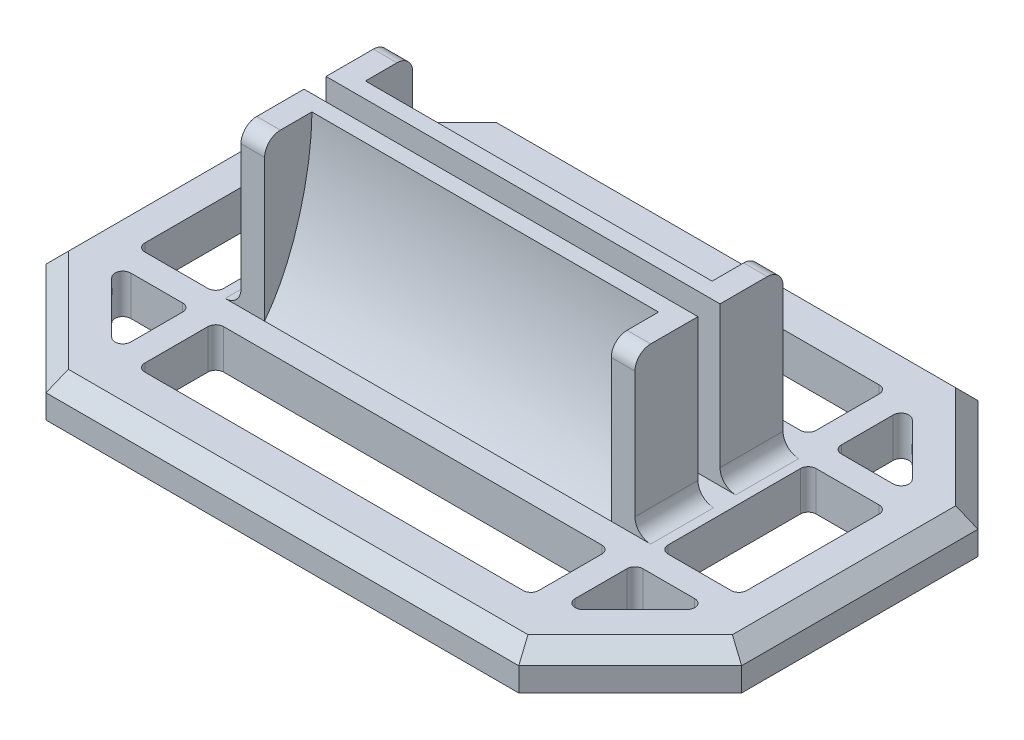
SolidWorks part; units mm, degrees
ref_plane "Front Plane" through (0, 0, 0) normal (0, 0, 1) x (1, 0, 0)
ref_plane "Top Plane" through (0, 0, 0) normal (0, 1, 0) x (1, 0, 0)
ref_plane "Right Plane" through (0, 0, 0) normal (1, 0, 0) x (0, 0, -1)
sketch "Sketch1" plane through (0, 0, 0) normal (0, 1, 0) x (1, 0, 0)
  line L0 (-38.1, 37.0105) -> (38.1, 37.0105)
  line L1 (38.1, 37.0105) -> (56.0605, 19.05)
  line L2 (56.0605, 19.05) -> (56.0605, -19.05)
  line L3 (56.0605, -19.05) -> (38.1, -37.0105)
  line L4 (38.1, -37.0105) -> (-38.1, -37.0105)
  line L5 (-38.1, -37.0105) -> (-56.0605, -19.05)
  line L6 (-56.0605, -19.05) -> (-56.0605, 19.05)
  line L7 (-56.0605, 19.05) -> (-38.1, 37.0105)
  line L8 (0, 37.0105) -> (0, -37.0105) construction
  point P10 (0, 0)
  dimension "D1" = 76.2
  dimension "D2" = 25.4
  dimension "D3" = 38.1
  dimension "D4" = 135
  dimension "D5" = 135
extrude "Boss-Extrude1" add sketch "Sketch1" along normal blind 6.35
sketch "Sketch2" plane through (0, 6.35, 0) normal (0, 1, 0) x (1, 0, 0)
  line L0 (-31.75, 1.778) -> (-31.75, 11.938)
  line L1 (-31.75, -1.778) -> (31.75, -1.778)
  line L2 (-31.75, -1.778) -> (-31.75, 1.778)
  line L3 (-31.75, 1.778) -> (31.75, 1.778)
  line L4 (31.75, -1.778) -> (31.75, 1.778)
  line L5 (-31.75, -1.778) -> (31.75, 1.778) construction
  line L6 (-31.75, 1.778) -> (31.75, -1.778) construction
  line L7 (-31.75, 11.938) -> (31.75, 11.938)
  line L8 (31.75, 11.938) -> (31.75, 1.778)
  line L9 (31.75, -1.778) -> (31.75, -11.938)
  line L10 (31.75, -11.938) -> (-31.75, -11.938)
  line L11 (-31.75, -11.938) -> (-31.75, -1.778)
  line L12 (35.8107, -16.002) -> (48.514, -16.002)
  line L13 (-31.75, -16.002) -> (31.75, -16.002)
  line L14 (-31.75, -16.002) -> (-31.75, -28.702)
  line L15 (-31.75, -28.702) -> (31.75, -28.702)
  line L16 (31.75, -16.002) -> (31.75, -28.702)
  line L17 (-31.75, 16.002) -> (31.75, 16.002)
  line L18 (-31.75, 16.002) -> (-31.75, 28.702)
  line L19 (-31.75, 28.702) -> (31.75, 28.702)
  line L20 (31.75, 16.002) -> (31.75, 28.702)
  line L21 (48.514, 11.938) -> (35.814, 11.938)
  line L22 (48.514, 11.938) -> (48.514, -11.938)
  line L23 (48.514, -11.938) -> (35.814, -11.938)
  line L24 (35.814, 11.938) -> (35.814, -11.938)
  line L25 (-35.814, 11.938) -> (-48.514, 11.938)
  line L26 (-35.814, 11.938) -> (-35.814, -11.938)
  line L27 (-35.814, -11.938) -> (-48.514, -11.938)
  line L28 (-48.514, 11.938) -> (-48.514, -11.938)
  line L29 (48.514, -16.002) -> (35.8107, -28.702)
  line L30 (35.8107, -28.702) -> (35.8107, -16.002)
  line L31 (35.814, 28.702) -> (35.814, 16.002)
  line L32 (35.814, 16.002) -> (48.514, 16.002)
  line L33 (48.514, 16.002) -> (35.814, 28.702)
  line L34 (-35.814, 16.002) -> (-35.814, 28.702)
  line L35 (-35.814, 28.702) -> (-48.514, 16.002)
  line L36 (-48.514, 16.002) -> (-35.814, 16.002)
  line L37 (-35.814, -28.702) -> (-35.814, -16.002)
  line L38 (-35.814, -16.002) -> (-48.514, -16.002)
  line L39 (-48.514, -16.002) -> (-35.814, -28.702)
  point P0 (0, 0)
  dimension "D1" = 3.556
  dimension "D2" = 63.5
  dimension "D3" = 10.16
  dimension "D4" = 12.7
  dimension "D5" = 63.5
  dimension "D6" = 4.064
  dimension "D7" = 4.064
  dimension "D8" = 12.7
  dimension "D9" = 4.064
  dimension "D10" = 4.064
extrude "Boss-Extrude2" add sketch "Sketch2" along normal blind 25.4 contours L11 L10 L9 L1 | L8 L7 L0 L3 region at (0, 6.35, -6.858) region at (0, 6.35, 6.858)
extrude "Cut-Extrude2" cut sketch "Sketch2<3>" against normal through all contours L21 L24 L23 L22 | L17 L20 L19 L18 | L25 L28 L27 L26 | L16 L13 L14 L15 | L35 L36 L34 | L32 L33 L31 | L30 L29 L12 | L38 L39 L37 region at (40.0451, 6.35, 20.2353) region at (0, 6.35, 22.352) region at (0, 6.35, -22.352) region at (42.164, 6.35, 0) region at (-42.164, 6.35, 0) region at (40.0473, 6.35, -20.2353) region at (-40.0473, 6.35, -20.2353) region at (-40.0473, 6.35, 20.2353)
sketch "Sketch2<3>" plane through (0, 6.35, 0) normal (0, 1, 0) x (1, 0, 0) same geometry as "Sketch2"
sketch "Sketch3" plane through (0, 0, 0) normal (1, 0, 0) x (0, 0, -1)
  line L0 (-11.938, 31.75) -> (-4.318, 31.75)
  line L1 (-1.778, 31.75) -> (-11.938, 31.75) construction
  line L2 (-11.938, 31.75) -> (-11.938, 6.35)
  line L3 (-11.938, 31.75) -> (-11.938, 6.35) construction
  line L5 (-19.05, 6.35) -> (19.05, 6.35) construction
  line L6 (11.938, 6.35) -> (11.938, 31.75)
  line L7 (11.938, 31.75) -> (4.318, 31.75)
  line L8 (11.938, 31.75) -> (1.778, 31.75) construction
  spline S0 degree 3 poles (-11.938, 6.35) (-6.8799, 12.8904) (-4.318, 23.9637) (-4.318, 31.75) knots 0 0 0 0 1 1 1 1
  spline S1 degree 3 poles (4.318, 31.75) (4.318, 21.9787) (6.8799, 14.3497) (11.938, 6.35) knots 0 0 0 0 1 1 1 1
  dimension "D1" = 5.08
  dimension "D2" = 7.62
  dimension "D3" = 15.24
  dimension "D4" = 7.62
  dimension "D5" = 5.08
  dimension "D6" = 15.24
extrude "Cut-Extrude1" cut sketch "Sketch3" against normal blind 27.94 and the other way blind 27.94
fillet "Fillet1" radius 2.54 4 edges at (-29.845, 31.75, 11.938) (-29.845, 31.75, -11.938) (29.845, 31.75, 11.938) (29.845, 31.75, -11.938)
chamfer "Chamfer1" distance 2.54 8 edges at (-47.0803, 6.35, -28.0303) (-56.0605, 6.35, 0) (-47.0803, 6.35, 28.0303) (0, 6.35, 37.0105) (47.0803, 6.35, 28.0303) (56.0605, 6.35, 0) (47.0803, 6.35, -28.0303) (0, 6.35, -37.0105)
fillet "Fillet2" radius 2.54 4 edges at (31.75, 6.35, 6.858) (-31.75, 6.35, 6.858) (-31.75, 6.35, -6.858) (31.75, 6.35, -6.858)
fillet "Fillet3" radius 1.27 28 edges at (-31.75, 3.175, -16.002) (-31.75, 3.175, -28.702) (31.75, 3.175, -16.002) (31.75, 3.175, -28.702) (35.814, 3.175, -16.002) (35.814, 3.175, -28.702) (48.514, 3.175, -16.002) (48.514, 3.175, 11.938) (35.814, 3.175, 11.938) (35.814, 3.175, -11.938) (48.514, 3.175, -11.938) (-35.814, 3.175, -28.702) (-35.814, 3.175, -16.002) (-48.514, 3.175, -16.002) (-48.514, 3.175, 11.938) (-48.514, 3.175, -11.938) (-35.814, 3.175, -11.938) (-35.814, 3.175, 11.938) (-48.514, 3.175, 16.002) (-35.814, 3.175, 16.002) (-35.814, 3.175, 28.702) (-31.75, 3.175, 28.702) (-31.75, 3.175, 16.002) (31.75, 3.175, 16.002) (31.75, 3.175, 28.702) (35.8107, 3.175, 28.702) (35.8107, 3.175, 16.002) (48.514, 3.175, 16.002)
